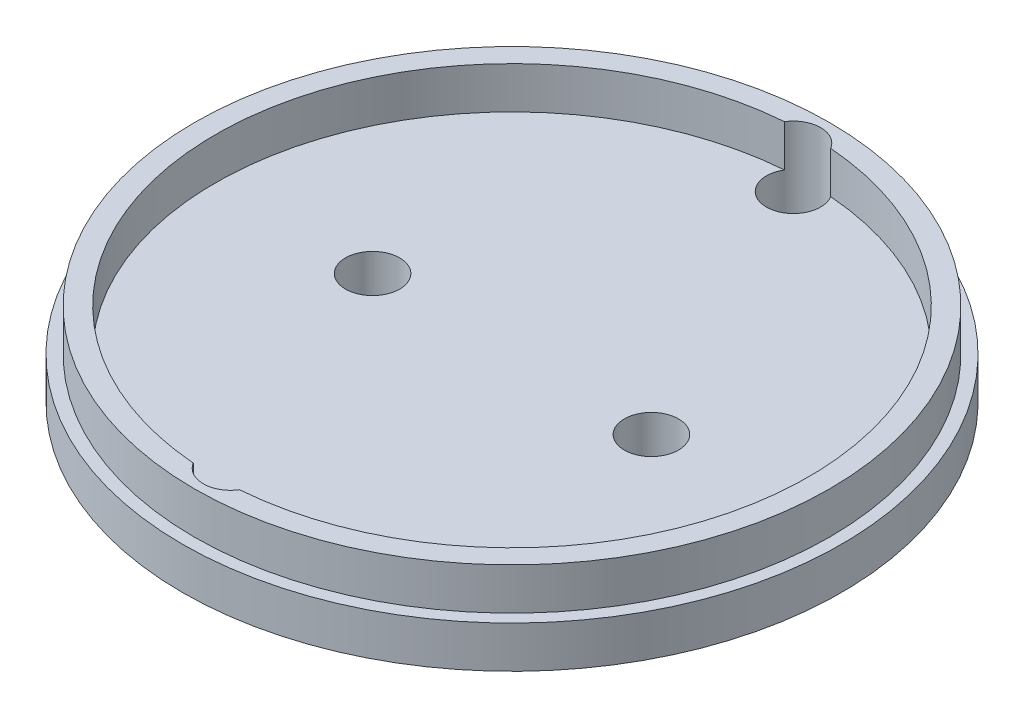
SolidWorks part; units mm, degrees
ref_plane "Front Plane" through (0, 0, 0) normal (0, 0, 1) x (1, 0, 0)
ref_plane "Top Plane" through (0, 0, 0) normal (0, 1, 0) x (1, 0, 0)
ref_plane "Right Plane" through (0, 0, 0) normal (1, 0, 0) x (0, 0, -1)
sketch "Sketch1" plane through (0, 0, 0) normal (0, 1, 0) x (1, 0, 0)
  circle A0 centre (0, 0) radius 39.4
  circle A1 centre (0, 0) radius 37.95
  circle A2 centre (0, 0) radius 35.45
  dimension "D1" = 78.8
  dimension "D2" = 75.9
  dimension "D3" = 2.5
extrude "Boss-Extrude1" add sketch "Sketch1" along normal blind 5 contours A1 A2 region at (-36.8766, 0, 0)
extrude "Boss-Extrude2" add sketch "Sketch1<4>" against normal blind 5 contours A1 A2 | A2 | A0 A1 region at (-38.2856, 0, 0) region at (-36.8766, 0, 0) region at (0, 0, 0)
sketch "Sketch1<4>" plane through (0, 0, 0) normal (0, 1, 0) x (1, 0, 0) same geometry as "Sketch1"
sketch "Sketch4" plane through (0, -5, 0) normal (0, -1, 0) x (1, 0, 0)
  line L0 (16.6687, 0) -> (-16.6688, 0) construction
  line L1 (0, 33.655) -> (0, -33.655) construction
  circle A0 centre (-16.6688, 0) radius 3.2385
  circle A1 centre (16.6687, 0) radius 3.2385
  circle A2 centre (0, 33.655) radius 3.2385
  circle A3 centre (0, -33.655) radius 3.2385
  point P5 (0, 0)
  point P11 (0, 0)
  dimension "D2" = 6.477
  dimension "D4" = 6.477
  dimension "D1" = 33.3375
  dimension "D3" = 67.31
extrude "Cut-Extrude1" cut sketch "Sketch4" against normal through all both and the other way through all
